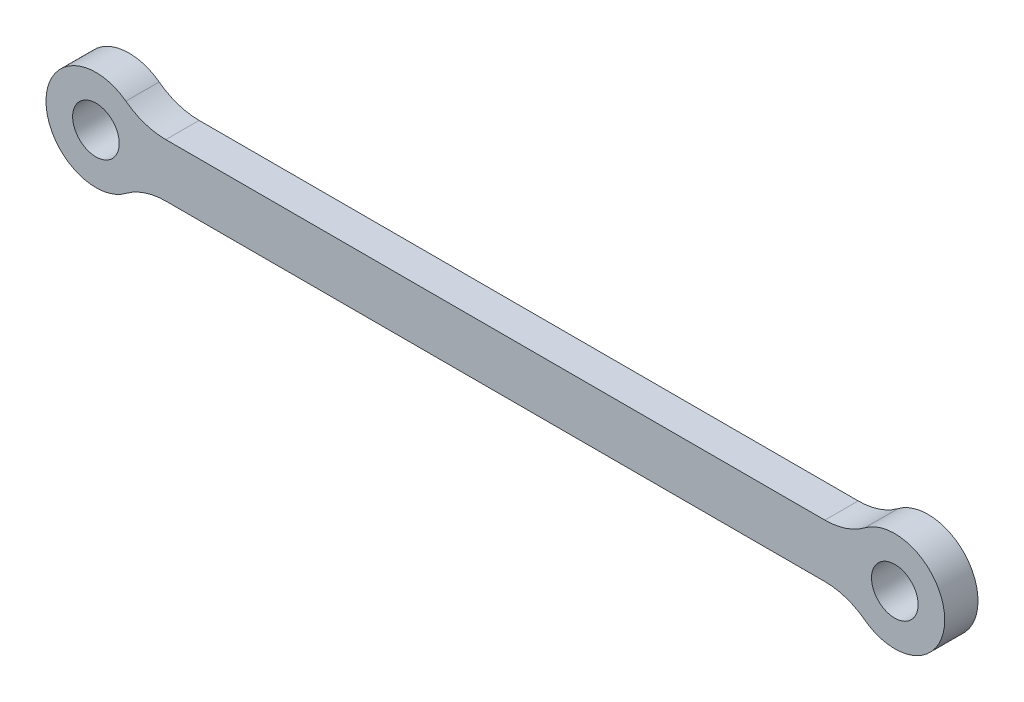
SolidWorks part; units mm, degrees
note: The reader was unsure of these and kept them because the rebuilt part matched: thickness of "Base-Flange1", "Sheet-Metal1".
ref_plane "Front Plane" through (0, 0, 0) normal (0, 0, 1) x (1, 0, 0)
ref_plane "Top Plane" through (0, 0, 0) normal (0, 1, 0) x (1, 0, 0)
ref_plane "Right Plane" through (0, 0, 0) normal (1, 0, 0) x (0, 0, -1)
sketch "Sketch1" plane through (0, 0, 0) normal (0, 0, 1) x (1, 0, 0)
  line L0 (-113.6557, 4) -> (-6.3443, 4)
  line L1 (-113.6557, -4) -> (-6.3443, -4)
  line L2 (-120, 0) -> (0, 0) construction
  line L3 (-60, 4) -> (-60, 0) construction
  line L4 (-60, 0) -> (-60, -4) construction
  circle A0 centre (-120, 0) radius 3.5
  arc A1 (-113.6557, 4) -> (-113.6557, -4) centre (-120, 0) ccw
  circle A2 centre (0, 0) radius 3.5
  arc A3 (-6.3443, -4) -> (-6.3443, 4) centre (0, 0) ccw
  arc A4 (-113.6557, -4) -> (-112.5, 0) centre (-120, 0) ccw construction
  arc A5 (-112.5, 0) -> (-113.6557, 4) centre (-120, 0) ccw construction
  arc A6 (-7.5, 0) -> (-6.3443, -4) centre (0, 0) ccw construction
  arc A7 (-6.3443, 4) -> (-7.5, 0) centre (0, 0) ccw construction
  dimension "D1" = 7
  dimension "D4" = 15
  dimension "D2" = 120
  dimension "D3" = 8
base flange "Base-Flange1" sketch "Sketch1" thickness 5 reverse thickness direction no parameters "D1"=0.7366
fillet "Fillet1" radius 10 4 edges at (-6.3443, 4, -2.5) (-6.3443, -4, -2.5) (-113.6557, -4, -2.5) (-113.6557, 4, -2.5)
sketch "Bend-Lines1" [suppressed] plane through (0, 0, 0) normal (0, 1, 0) x (1, 0, 0)
sketch "Bounding-Box1" [suppressed] plane through (0, 0, 0) normal (0, 1, 0) x (1, 0, 0)
sheet metal parameters "Sheet-Metal1" thickness 5 parameters "D1"=0.7366
flat pattern "Flat-Pattern1" [suppressed]
sketch "Bend-Lines2" plane through (0, 0, 0) normal (0, 1, 0) x (1, 0, 0)
sketch3d "Bounding-Box2" [suppressed]
  line L0 (-7.5, 7.5, 0) -> (127.5, 7.5, 0) construction
  line L1 (-7.5, -7.5, 0) -> (127.5, -7.5, 0) construction
  line L2 (-7.5, 7.5, 0) -> (-7.5, -7.5, 0) construction
  line L3 (127.5, 7.5, 0) -> (127.5, -7.5, 0) construction
